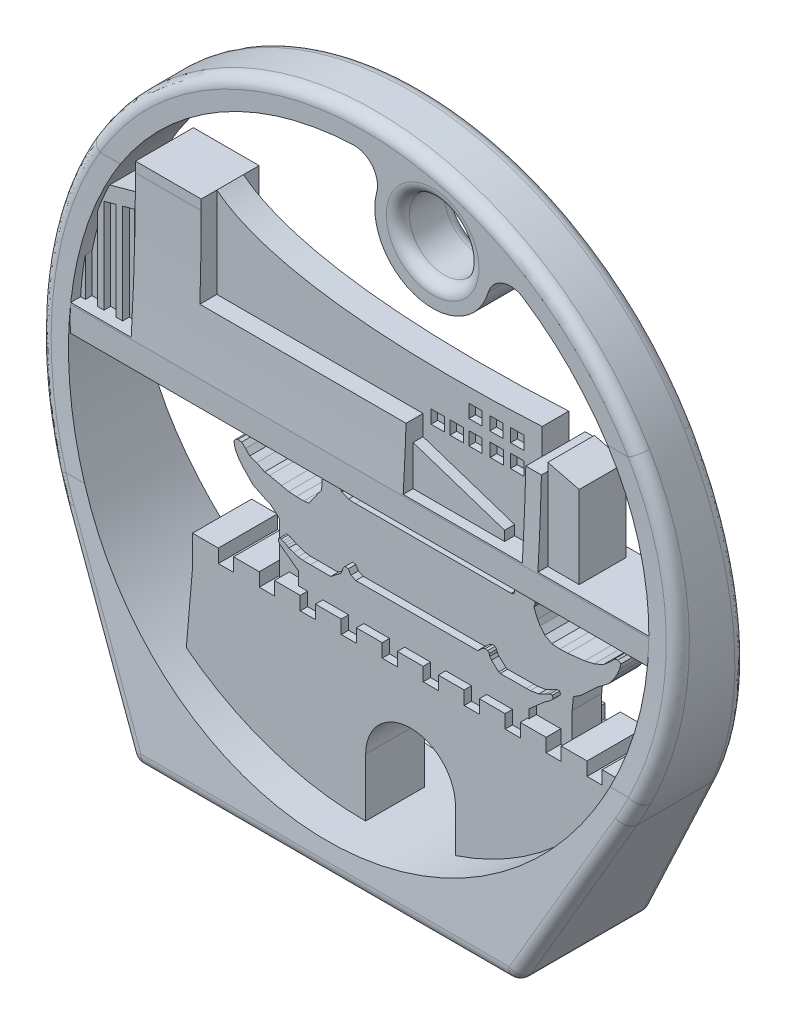
SolidWorks part; units mm, degrees
ref_plane "前视基准面" through (0, 0, 0) normal (0, 0, 1) x (1, 0, 0)
ref_plane "上视基准面" through (0, 0, 0) normal (0, 1, 0) x (1, 0, 0)
ref_plane "右视基准面" through (0, 0, 0) normal (1, 0, 0) x (0, 0, -1)
other "Configuration Table"
sketch "草图3" plane through (0, 0, 0) normal (0, 0, 1) x (1, 0, 0)
  line L0 (-24.2647, -12.9412) -> (-16.5, -27.5)
  line L1 (-16.5, -27.5) -> (16.5, -27.5)
  line L2 (16.5, -27.5) -> (24.2647, -12.9412)
  circle A0 centre (0, 0) radius 27.5
  circle A1 centre (0, 0) radius 25
  point P7 (0, -27.5)
  dimension "D1" = 55
  dimension "D2" = 50
  dimension "D3" = 33
extrude "凸台-拉伸2" add sketch "草图3" along normal blind 15 contours A0 L0 L1 | A0 L1 L2 | A0 A1 region at (-14.6613, -24.4356, 0) region at (-6.4811, 25.9243, 0) region at (14.6613, -24.4356, 0)
sketch "草图4" plane through (0, 0, 0) normal (1, 0, 0) x (0, 0, -1)
  line L0 (-8.5, 27.5) -> (-8.5, 13.5047)
  line L1 (-9.9443, -10.4879) -> (-12, -27.5)
  line L2 (-3.5, 27.5) -> (-3.5, 13.5047)
  line L3 (-2.0557, -10.4879) -> (0, -27.5)
  line L5 (16.5152, 37.1788) -> (-3.5, 27.5)
  line L6 (-12, -27.5) -> (-28.6636, -43.5847)
  line L8 (-8.5, -27.5) -> (-3.5, -27.5)
  line L9 (-15, -27.5) -> (0, -27.5) construction
  line L10 (-8.5, -27.5) -> (-6.9647, -14.7941)
  line L12 (-5.0353, -14.7941) -> (-3.5, -27.5)
  line L13 (-6, 15.3825) -> (-6, -28.8471) construction
  line L14 (0, -27.5) -> (0, -12.9412) construction
  line L15 (-8.5, 27.5) -> (-29.4388, 38.1578)
  line L16 (-29.4388, 38.1578) -> (-28.6636, -43.5847)
  line L17 (0, -27.5) -> (20.1867, -41.4741)
  line L18 (20.1867, -41.4741) -> (16.5152, 37.1788)
  line L19 (0, 27.5) -> (-15, 27.5) construction
  arc A2 (-5.0353, -14.7941) -> (-6.9647, -14.7941) centre (-6, -14.9107) ccw
  arc A3 (-3.5, 13.5047) -> (-2.0557, -10.4879) centre (196.5, 13.5047) ccw
  arc A4 (-9.9443, -10.4879) -> (-8.5, 13.5047) centre (-208.5, 13.5047) ccw
  point P56 (-3.5, 1.4649)
  point P59 (-8.5, 1.4649)
  dimension "D2" = 200
  dimension "D6" = 5
  dimension "D7" = 0.9717
  dimension "D1" = 5
  dimension "D3" = 3.5
  dimension "D4" = 3.5
  dimension "D5" = 6
extrude "切除-拉伸1" cut sketch "草图4" against normal through all both and the other way through all contours L2 L3 L5 | L0 A4 L1 L6 L16 L15 region at (0, -0.7928, -8.5347)
move or copy body "实体-移动/复制1" bodies to move or copy 108 copy no translate (0, 0, -6) parameters "D1"=0, "D2"=0, "D3"=6
sketch "草图6" plane through (0, 0, 0) normal (0, 0, 1) x (1, 0, 0)
  line L0 (-23.3587, 45.4654) -> (203.3079, 45.4654) construction
  line L1 (-76.39, -48.3201) -> (-73.7705, -48.3201)
  line L2 (-73.7705, -48.3201) -> (-73.7705, -49.6853)
  line L3 (-73.7705, -49.6853) -> (-72.2278, -49.6853)
  line L4 (-72.2278, -49.6853) -> (-72.2278, -48.3201)
  line L5 (-72.2278, -48.3201) -> (-69.6083, -48.3201)
  line L6 (-69.6083, -48.3201) -> (-69.6083, -49.6853)
  line L7 (-69.6083, -49.6853) -> (-68.0656, -49.6853)
  line L8 (-68.0656, -49.6853) -> (-68.0656, -48.3201)
  line L9 (-68.0656, -48.3201) -> (-65.4461, -48.3201)
  line L10 (-65.4461, -48.3201) -> (-65.4461, -49.6853)
  line L11 (-65.4461, -49.6853) -> (-63.9034, -49.6853)
  line L12 (-63.9034, -49.6853) -> (-63.9034, -48.3201)
  line L13 (-63.9034, -48.3201) -> (-61.2839, -48.3201)
  line L14 (-61.2839, -48.3201) -> (-61.2839, -49.6853)
  line L15 (-61.2839, -49.6853) -> (-59.7412, -49.6853)
  line L16 (-59.7412, -49.6853) -> (-59.7412, -48.3201)
  line L17 (-59.7412, -48.3201) -> (-57.1217, -48.3201)
  line L18 (-57.1217, -48.3201) -> (-57.1217, -49.6853)
  line L19 (-57.1217, -49.6853) -> (-55.579, -49.6853)
  line L20 (-55.579, -49.6853) -> (-55.579, -48.3201)
  line L21 (-55.579, -48.3201) -> (-52.9595, -48.3201)
  line L22 (-52.9595, -48.3201) -> (-52.9595, -49.6853)
  line L23 (-52.9595, -49.6853) -> (-51.4168, -49.6853)
  line L24 (-51.4168, -49.6853) -> (-51.4168, -48.3201)
  line L25 (-51.4168, -48.3201) -> (-48.7973, -48.3201)
  line L26 (-48.7973, -48.3201) -> (-48.7973, -49.6853)
  line L27 (-48.7973, -49.6853) -> (-47.2546, -49.6853)
  line L28 (-47.2546, -49.6853) -> (-47.2546, -48.3201)
  line L29 (-47.2546, -48.3201) -> (-44.6351, -48.3201)
  line L30 (-44.6351, -48.3201) -> (-44.6351, -49.6853)
  line L31 (-44.6351, -49.6853) -> (-43.0924, -49.6853)
  line L32 (-43.0924, -49.6853) -> (-43.0924, -48.3201)
  line L33 (-43.0924, -48.3201) -> (-40.4729, -48.3201)
  line L34 (-40.4729, -48.3201) -> (-40.4729, -49.6853)
  line L35 (-40.4729, -49.6853) -> (-38.9302, -49.6853)
  line L36 (-38.9302, -49.6853) -> (-38.9302, -48.3201)
  line L37 (-38.9302, -48.3201) -> (-36.3107, -48.3201)
  line L38 (-36.3107, -48.3201) -> (-36.3107, -49.6853)
  line L39 (-36.3107, -49.6853) -> (-34.768, -49.6853)
  line L40 (-34.768, -49.6853) -> (-34.768, -48.3201)
  line L41 (-34.768, -48.3201) -> (-32.1486, -48.3201)
  line L42 (-76.39, -48.3201) -> (-76.39, -51.3923)
  line L43 (-76.39, -51.3923) -> (-77.5562, -64.9)
  line L44 (-77.5562, -64.9) -> (-30.9199, -64.9)
  line L45 (-30.9199, -64.9) -> (-32.1486, -51.3923)
  line L46 (-32.1486, -51.3923) -> (-32.1486, -48.3201)
  line L47 (-54.238, -64.9) -> (-54.238, -68.8519) construction
  line L48 (-66.3815, -48.3201) -> (-66.3815, -47.0098)
  line L50 (-58.7984, -58.9541) -> (-58.7984, -64.9)
  line L51 (-58.7984, -64.9) -> (-49.6777, -64.9)
  line L52 (-49.6777, -58.9541) -> (-49.6777, -64.9)
  line L53 (-66.3815, -47.0098) -> (-68.227, -45.644)
  line L54 (-68.227, -45.644) -> (-68.3633, -45.4879)
  line L55 (-68.3633, -45.4879) -> (-68.3959, -45.3497)
  line L56 (-68.3959, -45.3497) -> (-68.3796, -45.1708)
  line L57 (-68.3796, -45.1708) -> (-68.3146, -45.0976)
  line L58 (-68.3146, -45.0976) -> (-68.1601, -45.1057)
  line L59 (-68.1601, -45.1057) -> (-67.9406, -45.1789)
  line L60 (-67.9406, -45.1789) -> (-67.778, -45.2602)
  line L61 (-67.778, -45.2602) -> (-67.5828, -45.3497)
  line L62 (-67.5828, -45.3497) -> (-67.3633, -45.4879)
  line L63 (-67.3633, -45.4879) -> (-66.8674, -45.6261)
  line L64 (-66.8674, -45.6261) -> (-66.4039, -45.7887)
  line L65 (-66.4039, -45.7887) -> (-65.9649, -45.8537)
  line L66 (-65.9649, -45.8537) -> (-65.16, -45.8537)
  line L67 (-65.16, -45.8537) -> (-63.103, -45.8619)
  line L68 (-63.103, -45.8619) -> (-62.0705, -45.0651)
  line L69 (-62.0705, -45.0651) -> (-61.9648, -44.8293)
  line L70 (-61.9648, -44.8293) -> (-61.8184, -44.4472)
  line L71 (-61.8184, -44.4472) -> (-61.6233, -44.2358)
  line L72 (-61.6233, -44.2358) -> (-61.3144, -44.2927)
  line L73 (-61.3144, -44.2927) -> (-61.0461, -44.7155)
  line L74 (-61.0461, -44.7155) -> (-60.5501, -44.9431)
  line L75 (-60.5501, -44.9431) -> (-48.1803, -44.9169)
  line L76 (-48.1803, -44.9169) -> (-47.9471, -44.7517)
  line L77 (-47.9471, -44.7517) -> (-47.7333, -44.5185)
  line L78 (-47.7333, -44.5185) -> (-47.4029, -44.3727)
  line L79 (-47.4029, -44.3727) -> (-47.16, -44.4116)
  line L80 (-47.16, -44.4116) -> (-46.9948, -44.5865)
  line L81 (-46.9948, -44.5865) -> (-46.9365, -44.8003)
  line L82 (-46.9365, -44.8003) -> (-46.7713, -45.0627)
  line L83 (-46.7713, -45.0627) -> (-46.0425, -45.7235)
  line L84 (-46.0425, -45.7235) -> (-45.8812, -45.7876)
  line L85 (-45.8812, -45.7876) -> (-43.2035, -45.7634)
  line L86 (-43.2035, -45.7634) -> (-42.8244, -45.7634)
  line L87 (-42.8244, -45.7634) -> (-41.9534, -45.6182)
  line L88 (-41.9534, -45.6182) -> (-41.2517, -45.2634)
  line L89 (-41.2517, -45.2634) -> (-40.8242, -45.0456)
  line L90 (-40.8242, -45.0456) -> (-40.5903, -45.0537)
  line L91 (-40.5903, -45.0537) -> (-40.5016, -45.3279)
  line L92 (-40.5016, -45.3279) -> (-40.7758, -45.6263)
  line L93 (-40.7758, -45.6263) -> (-41.0339, -45.8118)
  line L94 (-41.0339, -45.8118) -> (-41.3646, -46.0296)
  line L95 (-41.3646, -46.0296) -> (-42.9643, -47.4419)
  line L96 (-42.9643, -47.4419) -> (-42.9643, -48.3201)
  line L97 (-69.033, -49.6853) -> (-69.033, -44.2605)
  line L98 (-69.033, -44.2605) -> (-69.0876, -44.0855)
  line L99 (-69.0876, -44.0855) -> (-69.9954, -43.309)
  line L100 (-69.9954, -43.309) -> (-70.5236, -43.0944)
  line L101 (-70.5236, -43.0944) -> (-71.0009, -42.8644)
  line L102 (-71.0009, -42.8644) -> (-71.7657, -42.4906)
  line L103 (-71.7657, -42.4906) -> (-72.1509, -42.0651)
  line L104 (-72.1509, -42.0651) -> (-72.7892, -41.4268)
  line L105 (-72.7892, -41.4268) -> (-73.1975, -40.8978)
  line L106 (-73.1975, -40.8978) -> (-73.508, -40.3285)
  line L107 (-73.508, -40.3285) -> (-73.623, -39.9778)
  line L108 (-73.623, -39.9778) -> (-73.6747, -39.5695)
  line L109 (-73.6747, -39.5695) -> (-73.462, -39.328)
  line L110 (-73.462, -39.328) -> (-73.2837, -39.282)
  line L111 (-73.2837, -39.282) -> (-72.9042, -39.3107)
  line L112 (-72.9042, -39.3107) -> (-72.5017, -39.6672)
  line L113 (-72.5017, -39.6672) -> (-72.0819, -40.1215)
  line L114 (-72.0819, -40.1215) -> (-71.3861, -40.3688)
  line L115 (-71.3861, -40.3688) -> (-70.557, -40.7592)
  line L116 (-70.557, -40.7592) -> (-70.0808, -40.842)
  line L117 (-70.0808, -40.842) -> (-68.8526, -41.1042)
  line L118 (-68.8526, -41.1042) -> (-68.1281, -41.2767)
  line L119 (-68.1281, -41.2767) -> (-67.3345, -41.325)
  line L120 (-67.3345, -41.325) -> (-66.5824, -41.3388)
  line L121 (-66.5824, -41.3388) -> (-66.058, -41.2629)
  line L122 (-66.058, -41.2629) -> (-65.1334, -39.9381)
  line L123 (-65.1334, -39.9381) -> (-64.809, -39.5241)
  line L124 (-64.809, -39.5241) -> (-64.7262, -38.9858)
  line L125 (-64.7262, -38.9858) -> (-64.7331, -38.5511)
  line L126 (-64.7331, -38.5511) -> (-64.5192, -37.8128)
  line L127 (-64.5192, -37.8128) -> (-64.1604, -37.3298)
  line L128 (-64.1604, -37.3298) -> (-63.8844, -37.2263)
  line L129 (-63.8844, -37.2263) -> (-63.4428, -37.3643)
  line L130 (-63.4428, -37.3643) -> (-63.015, -37.9853)
  line L131 (-63.015, -37.9853) -> (-62.7183, -38.6339)
  line L132 (-62.7183, -38.6339) -> (-62.042, -38.8961)
  line L133 (-62.042, -38.8961) -> (-61.3313, -38.9375)
  line L134 (-61.3313, -38.9375) -> (-45.5136, -38.9218)
  line L135 (-45.5136, -38.9218) -> (-45.259, -38.8454)
  line L136 (-45.259, -38.8454) -> (-45.1571, -38.5568)
  line L137 (-45.1571, -38.5568) -> (-45.1741, -38.2852)
  line L138 (-45.1741, -38.2852) -> (-44.9279, -38.022)
  line L139 (-44.9279, -38.022) -> (-44.5035, -37.3769)
  line L140 (-44.5035, -37.3769) -> (-44.164, -37.1817)
  line L141 (-44.164, -37.1817) -> (-43.5783, -37.5297)
  line L142 (-43.5783, -37.5297) -> (-43.1539, -38.3701)
  line L143 (-43.1539, -38.3701) -> (-43.069, -38.6247)
  line L144 (-43.069, -38.6247) -> (-43.2218, -38.9812)
  line L145 (-43.2218, -38.9812) -> (-42.8319, -39.8582)
  line L146 (-42.8319, -39.8582) -> (-42.5813, -40.326)
  line L147 (-42.5813, -40.326) -> (-42.1051, -40.9023)
  line L148 (-42.1051, -40.9023) -> (-41.3868, -41.2949)
  line L149 (-41.3868, -41.2949) -> (-40.5765, -41.3618)
  line L150 (-40.5765, -41.3618) -> (-39.7663, -41.3283)
  line L151 (-39.7663, -41.3283) -> (-38.0539, -41.1362)
  line L152 (-38.0539, -41.1362) -> (-37.0849, -40.9107)
  line L153 (-37.0849, -40.9107) -> (-36.1827, -40.5431)
  line L154 (-36.1827, -40.5431) -> (-35.3057, -39.7914)
  line L155 (-35.3057, -39.7914) -> (-35.0551, -39.499)
  line L156 (-35.0551, -39.499) -> (-34.6708, -39.3653)
  line L157 (-34.6708, -39.3653) -> (-34.3785, -39.5742)
  line L158 (-34.3785, -39.5742) -> (-34.4871, -40.0503)
  line L159 (-34.4871, -40.0503) -> (-34.7627, -40.6851)
  line L160 (-34.7627, -40.6851) -> (-35.1052, -41.2949)
  line L161 (-35.1052, -41.2949) -> (-35.6147, -41.9298)
  line L162 (-35.6147, -41.9298) -> (-36.7675, -42.8068)
  line L163 (-36.7675, -42.8068) -> (-37.5443, -43.5252)
  line L164 (-37.5443, -43.5252) -> (-38.4799, -44.4023)
  line L165 (-38.4799, -44.4023) -> (-39.1982, -44.8534)
  line L166 (-39.1982, -44.8534) -> (-39.3206, -46.1392)
  line L167 (-39.3206, -46.1392) -> (-39.3206, -49.6853)
  line L168 (-77.5562, -64.9) -> (-78.3282, -73.843)
  line L169 (-78.3282, -73.843) -> (-30.1064, -73.843)
  line L170 (-30.1064, -73.843) -> (-30.9199, -64.9)
  arc A0 (-49.6777, -58.9541) -> (-58.7984, -58.9541) centre (-54.238, -58.9541) ccw
  dimension "D1" = 46.6363
extrude "凸台-拉伸3" add sketch "草图6" along normal mid plane 3 separate body contours L167 L166 L165 L164 L163 L162 L161 L160 L159 L158 L157 L156 L155 L154 L153 L152 L151 L150 L149 L148 L147 L146 L145 L144 L143 L142 L141 L140 L139 L138 L137 L136 L135 L134 L133 L132 L131 L130 L129 L128 L127 L126 L125 L124 L123 L122 L121 L120 L119 L118 L117 region at (-53.9009, -42.5531, 0)
extrude "凸台-拉伸4" add sketch "草图6<4>" along normal mid plane 4.5 contours L96 L95 L94 L93 L92 L91 L90 L89 L88 L87 L86 L85 L84 L83 L82 L81 L80 L79 L78 L77 L76 L75 L74 L73 L72 L71 L70 L69 L68 L67 L66 L65 L64 L63 L62 L61 L60 L59 L58 L57 L56 L55 L54 L53 L48 L9 L10 L11 L12 L13 L14 region at (-54.465, -47.0008, 0)
sketch "草图6<4>" plane through (0, 0, 0) normal (0, 0, 1) x (1, 0, 0) same geometry as "草图6"
extrude "凸台-拉伸5" add sketch "草图6<5>" along normal mid plane 6 contours A0 L52 L44 L45 L46 L41 L40 L39 L38 L37 L36 L35 L34 L33 L32 L31 L30 L29 L28 L27 L26 L25 L24 L23 L22 L21 L20 L19 L18 L17 L16 L15 L14 L13 L12 L11 L10 L9 L8 L7 L6 L5 L4 L3 L2 L1 L42 | L169 L170 L44 L168 region at (-75.0803, -48.8151, 0) region at (-54.2276, -69.3964, 0)
sketch "草图6<5>" plane through (0, 0, 0) normal (0, 0, 1) x (1, 0, 0) same geometry as "草图6"
move or copy body "实体-移动/复制2" bodies to move or copy 114 copy no translate (58.3038, 39.0049, 0) parameters "D1"=58.3038, "D2"=39.0049, "D3"=0
scale "缩放比例1" bodies to scale 114 scale about centroid uniform scaling yes scale factor 0.85
sketch "草图8" plane through (0, 0, 0) normal (0, 0, 1) x (1, 0, 0)
  line L0 (-24.1949, 90.5328) -> (333.1385, 90.5328) construction
  line L1 (-26.7057, -5.5616) -> (131.2943, -5.5616) construction
  line L2 (126.5792, 406.192) -> (979.9125, 406.192) construction
  line L3 (-86.1144, -63.6079) -> (-48.5829, -63.6079)
  line L4 (-48.5829, -63.6079) -> (-48.5829, -57.422)
  line L5 (-48.5829, -57.422) -> (-50.943, -56.8357)
  line L6 (-50.943, -56.8357) -> (-50.943, -63.6079)
  line L7 (-50.943, -57.422) -> (-52.1156, -57.422)
  line L8 (-52.1156, -63.6079) -> (-52.1156, -55.4677)
  line L9 (-86.1144, -63.6079) -> (-86.1144, -55.8713)
  line L10 (-86.1144, -55.8713) -> (-81.4805, -54.5993)
  line L11 (-81.4805, -54.5993) -> (-81.4805, -52.3044)
  line L12 (-81.4805, -52.3044) -> (-76.5454, -52.3044)
  line L13 (-76.5454, -52.3044) -> (-76.5454, -63.6079)
  line L14 (-81.4805, -54.5993) -> (-81.4805, -63.6079)
  line L15 (-76.5454, -59.0921) -> (-61.0588, -59.0921)
  line L16 (-61.0588, -59.0921) -> (-61.0588, -63.6079)
  line L17 (-61.0588, -60.6009) -> (-54.1874, -62.8775)
  line L18 (-54.1874, -62.8775) -> (-54.1874, -63.6079)
  line L20 (-89.5754, -63.6079) -> (-40.6679, -63.6079)
  line L21 (-89.5754, -63.6079) -> (-89.5754, -65.6079)
  line L22 (-89.5754, -65.6079) -> (-40.6679, -65.6079)
  line L23 (-40.6679, -63.6079) -> (-40.6679, -65.6079)
  spline S0 degree 3 poles (-76.5454, -52.3044) (-72.6624, -55.428) (-62.4102, -56.0454) (-52.1156, -55.4677) knots 0 0 0 0 1 1 1 1
  dimension "D1" = 2
  dimension "D2" = 0
extrude "凸台-拉伸6" add sketch "草图8" along normal mid plane 2 separate body contours L9 | S0 L13 L15 L16 L17 L18 L3 L8 region at (-63.4137, -57.8065, 0)
extrude "凸台-拉伸7" add sketch "草图8<3>" along normal mid plane 3.5 contours L18 L17 L16 L3 | L14 L10 L9 L3 | L5 L6 L3 L4 region at (-83.7388, -59.4136, 0) region at (-58.3206, -62.558, 0) region at (-49.7808, -60.3662, 0)
sketch "草图8<3>" plane through (0, 0, 0) normal (0, 0, 1) x (1, 0, 0) same geometry as "草图8"
extrude "凸台-拉伸8" add sketch "草图8<4>" along normal mid plane 5 contours L11 L14 L3 L13 L12 | L16 L15 L13 L3 | L8 L3 L6 L7 region at (-79.013, -57.9561, 0) region at (-68.8021, -61.35, 0) region at (-51.5293, -60.515, 0)
sketch "草图8<4>" plane through (0, 0, 0) normal (0, 0, 1) x (1, 0, 0) same geometry as "草图8"
extrude "凸台-拉伸10" add sketch "草图8<7>" along normal mid plane 5 contours L21 L22 L23 L20
sketch "草图8<7>" plane through (0, 0, 0) normal (0, 0, 1) x (1, 0, 0) same geometry as "草图8"
sketch "草图9" plane through (0, 0, 1.75) normal (0, 0, 1) x (1, 0, 0)
  line L0 (-85.6703, -56.9085) -> (-81.9703, -55.8928)
  line L1 (-86.1144, -55.8713) -> (-81.4805, -54.5993) construction
  line L2 (-85.6703, -56.9085) -> (-85.6703, -63.6079)
  line L4 (-84.7703, -56.6614) -> (-84.7703, -63.6079)
  line L5 (-84.2703, -56.5242) -> (-84.2703, -63.6079)
  line L6 (-83.3703, -56.2771) -> (-83.3703, -63.6079)
  line L7 (-81.9703, -55.8928) -> (-81.9703, -63.6079)
  line L8 (-82.8703, -56.1399) -> (-82.8703, -63.6079)
  line L9 (-85.6703, -63.6079) -> (-81.9703, -63.6079)
  line L10 (-86.1144, -63.6079) -> (-48.5829, -63.6079) construction
  dimension "D1" = 0.9
  dimension "D2" = 0.9
  dimension "D3" = 0.9
  dimension "D4" = 0.5
  dimension "D5" = 0.5
extrude "切除-拉伸10" cut sketch "草图9" against normal blind 0.5 contours L4 L0 L2 | L6 L0 L5 | L0 L8 L7 region at (-85.2175, -60.1961, 1.75) region at (-83.8177, -60.0039, 1.75) region at (-82.4178, -59.8118, 1.75)
sketch "草图10" plane through (0, 0, 1) normal (0, 0, 1) x (1, 0, 0)
  line L0 (-54.4946, -58.3912) -> (-53.4946, -58.3912)
  line L1 (-54.4847, -56.7108) -> (-53.4847, -56.7108)
  line L2 (-54.4847, -56.7108) -> (-54.4847, -57.7108)
  line L3 (-54.4847, -57.7108) -> (-53.4847, -57.7108)
  line L4 (-53.4847, -56.7108) -> (-53.4847, -57.7108)
  line L5 (-54.4946, -58.3912) -> (-54.4946, -59.3912)
  line L6 (-54.4946, -59.3912) -> (-53.4946, -59.3912)
  line L7 (-53.4946, -58.3912) -> (-53.4946, -59.3912)
  line L8 (-56.0465, -56.7207) -> (-55.0465, -56.7207)
  line L9 (-56.0465, -56.7207) -> (-56.0465, -57.7207)
  line L10 (-56.0465, -57.7207) -> (-55.0465, -57.7207)
  line L11 (-55.0465, -56.7207) -> (-55.0465, -57.7207)
  line L12 (-56.0197, -58.433) -> (-55.0197, -58.433)
  line L13 (-56.0197, -58.433) -> (-56.0197, -59.433)
  line L14 (-56.0197, -59.433) -> (-55.0197, -59.433)
  line L15 (-55.0197, -58.433) -> (-55.0197, -59.433)
  line L16 (-59.0389, -58.4905) -> (-58.0389, -58.4905)
  line L17 (-59.0389, -58.4905) -> (-59.0389, -59.4905)
  line L18 (-59.0389, -59.4905) -> (-58.0389, -59.4905)
  line L19 (-58.0389, -58.4905) -> (-58.0389, -59.4905)
  line L20 (-57.6196, -58.4823) -> (-56.6196, -58.4823)
  line L21 (-57.6196, -58.4823) -> (-57.6196, -59.4823)
  line L22 (-57.6196, -59.4823) -> (-56.6196, -59.4823)
  line L23 (-56.6196, -58.4823) -> (-56.6196, -59.4823)
  line L24 (-60.4582, -58.4905) -> (-59.4582, -58.4905)
  line L25 (-60.4582, -58.4905) -> (-60.4582, -59.4905)
  line L26 (-60.4582, -59.4905) -> (-59.4582, -59.4905)
  line L27 (-59.4582, -58.4905) -> (-59.4582, -59.4905)
  line L28 (-57.6196, -56.702) -> (-56.6196, -56.702)
  line L29 (-57.6196, -56.702) -> (-57.6196, -57.702)
  line L30 (-57.6196, -57.702) -> (-56.6196, -57.702)
  line L31 (-56.6196, -56.702) -> (-56.6196, -57.702)
  dimension "D1" = 1
extrude "切除-拉伸11" cut sketch "草图10" against normal blind 0.5
scale "缩放比例2" bodies to scale 130 scale about centroid uniform scaling yes scale factor 1.15
move or copy body "实体-移动/复制4" bodies to move or copy 131 copy no translate (63.6907, 65.3638, 0) parameters "D1"=63.6907, "D2"=65.3638, "D3"=0
sketch "草图7" plane through (0, 0, 0) normal (0, 0, 1) x (1, 0, 0)
  line L0 (16.5, -27.5) -> (24.2647, -12.9412) construction
  line L1 (-24.2647, -12.9412) -> (-16.5, -27.5) construction
  line L2 (-16.5, -27.5) -> (16.5, -27.5) construction
  line L3 (16.5, -27.5) -> (24.2647, -12.9412)
  line L4 (-24.2647, -12.9412) -> (-16.5, -27.5)
  line L5 (-16.5, -27.5) -> (16.5, -27.5)
  arc A1 (-23.9556, 13.5047) -> (-25.4215, -10.4879) centre (0, 0) ccw construction
  arc A2 (24.2647, -12.9412) -> (25.4215, -10.4879) centre (0, 0) ccw construction
  arc A4 (-25.4215, -10.4879) -> (-24.2647, -12.9412) centre (0, 0) ccw construction
  arc A6 (25.4215, -10.4879) -> (23.9556, 13.5047) centre (0, 0) ccw construction
  arc A7 (23.9556, 13.5047) -> (-23.9556, 13.5047) centre (0, 0) ccw construction
  arc A10 (-23.9556, 13.5047) -> (-25.4215, -10.4879) centre (0, 0) ccw
  arc A11 (24.2647, -12.9412) -> (25.4215, -10.4879) centre (0, 0) ccw
  arc A13 (-25.4215, -10.4879) -> (-24.2647, -12.9412) centre (0, 0) ccw
  arc A15 (25.4215, -10.4879) -> (23.9556, 13.5047) centre (0, 0) ccw
  arc A16 (23.9556, 13.5047) -> (-23.9556, 13.5047) centre (0, 0) ccw
extrude "切除-拉伸9" cut sketch "草图7" against normal through all both and the other way through all flip side to cut
sketch "草图11" plane through (0, 0, 0) normal (1, 0, 0) x (0, 0, -1)
  line L0 (4.2408, -12.9412) -> (3.9443, -10.4879) construction
  line L1 (2.5, 13.5047) -> (2.5, 27.5) construction
  line L2 (4.2408, -12.9412) -> (3.9443, -10.4879) construction
  line L4 (-3.9443, -10.4879) -> (-4.2408, -12.9412) construction
  line L5 (-2.5, 27.5) -> (-2.5, 13.5047) construction
  line L6 (-3.9443, -10.4879) -> (-4.2408, -12.9412) construction
  line L7 (-6, -27.5) -> (6, -27.5) construction
  line L8 (6, -27.5) -> (4.2408, -12.9412) construction
  line L9 (-4.2408, -12.9412) -> (-6, -27.5) construction
  line L10 (4.2408, -12.9412) -> (3.9443, -10.4879)
  line L11 (2.5, 13.5047) -> (2.5, 27.5)
  line L12 (4.2408, -12.9412) -> (3.9443, -10.4879)
  line L14 (-3.9443, -10.4879) -> (-4.2408, -12.9412)
  line L15 (-2.5, 27.5) -> (-2.5, 13.5047)
  line L16 (-3.9443, -10.4879) -> (-4.2408, -12.9412)
  line L17 (-6, -27.5) -> (6, -27.5)
  line L18 (6, -27.5) -> (4.2408, -12.9412)
  line L19 (-4.2408, -12.9412) -> (-6, -27.5)
  line L20 (2.5, 27.5) -> (-2.5, 27.5)
  arc A0 (2.5, 13.5047) -> (3.9443, -10.4879) centre (202.5, 13.5047) ccw construction
  arc A1 (2.5, 13.5047) -> (3.9443, -10.4879) centre (202.5, 13.5047) ccw construction
  arc A2 (-3.9443, -10.4879) -> (-2.5, 13.5047) centre (-202.5, 13.5047) ccw construction
  arc A3 (-3.9443, -10.4879) -> (-2.5, 13.5047) centre (-202.5, 13.5047) ccw construction
  arc A4 (2.5, 13.5047) -> (3.9443, -10.4879) centre (202.5, 13.5047) ccw
  arc A5 (2.5, 13.5047) -> (3.9443, -10.4879) centre (202.5, 13.5047) ccw
  arc A6 (-3.9443, -10.4879) -> (-2.5, 13.5047) centre (-202.5, 13.5047) ccw
  arc A7 (-3.9443, -10.4879) -> (-2.5, 13.5047) centre (-202.5, 13.5047) ccw
extrude "切除-拉伸12" cut sketch "草图11" against normal through all both and the other way through all flip side to cut contours A6 L14 L19 L17 L18 L10 A4 L11 L20 L15 region at (0, -4.711, 0)
combine bodies "组合2" operation type add bodies to combine 134 136 111
sketch "草图12" plane through (0, 0, 0) normal (0, 0, 1) x (1, 0, 0)
  circle A0 centre (5.9265, 21.1867) radius 3
  circle A1 centre (5.9265, 21.1867) radius 5
  arc A2 (21.0386, 13.5047) -> (-21.0386, 13.5047) centre (0, 0) ccw construction
  dimension "D1" = 6
  dimension "D2" = 10
extrude "凸台-拉伸11" add sketch "草图12" along normal mid plane 5
fillet "圆角1" radius 1 10 edges at (24.8734, -11.7288, 4.0943) (24.8734, -11.7288, -4.0943) (20.3824, -20.2206, 5.1204) (20.3824, -20.2206, -5.1204) (-16.5, -27.5, 0) (0, -27.5, 6) (16.5, -27.5, 0) (0, -27.5, -6) (8.9265, 21.1867, 2.5) (8.9265, 21.1867, -2.5)
fillet "圆角2" radius 2 2 edges at (10.7282, 22.5811, 0) (2.5453, 24.8701, 0)
